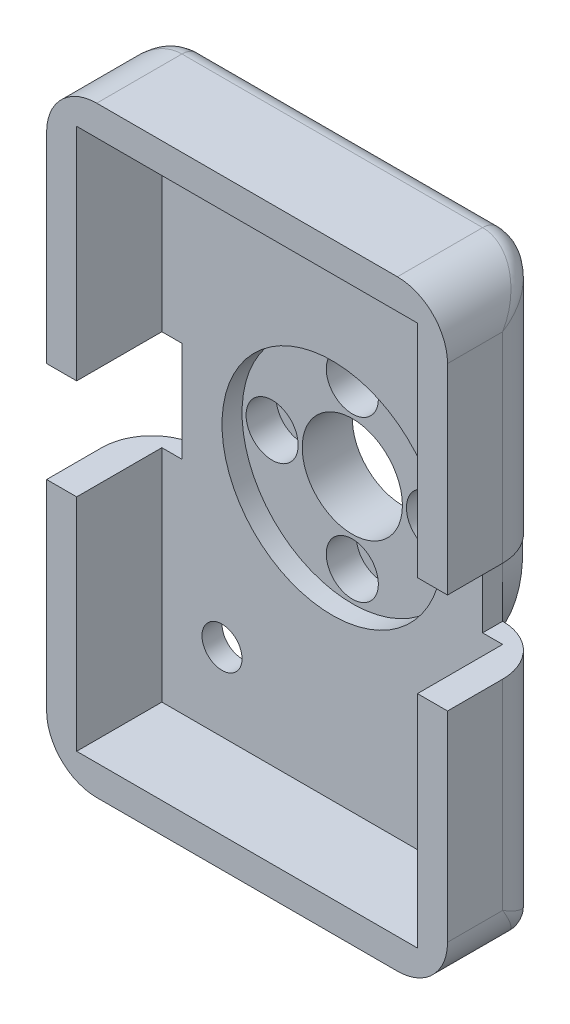
SolidWorks part; units mm, degrees
ref_plane "Front Plane" through (0, 0, 0) normal (0, 0, 1) x (1, 0, 0)
ref_plane "Top Plane" through (0, 0, 0) normal (0, 1, 0) x (1, 0, 0)
ref_plane "Right Plane" through (0, 0, 0) normal (1, 0, 0) x (0, 0, -1)
sketch "Sketch1" plane through (0, 0, 0) normal (0, 0, 1) x (1, 0, 0)
  line L0 (0, -11.559) -> (0, -10.441) construction
  circle A0 centre (0, -3) radius 1.25
  circle A1 centre (-8, -11) radius 1.25
  circle A2 centre (0, -19) radius 1.25
  circle A3 centre (8, -11) radius 1.25
  circle A4 centre (0, -11) radius 11
  spline S0 degree 3 poles (0.1424, -11.5375) (0.0489, -11.5664) (-0.0489, -11.5664) (-0.1424, -11.5375) knots 5.98544 5.98544 5.98544 5.98544 6.580931 6.580931 6.580931 6.580931 weights 1 0.970667 0.970667 1 construction
  spline S1 degree 3 poles (-0.1424, -10.4625) (-0.0489, -10.4336) (0.0489, -10.4336) (0.1424, -10.4625) knots 5.98544 5.98544 5.98544 5.98544 6.580931 6.580931 6.580931 6.580931 weights 1 0.970667 0.970667 1 construction
  dimension "D1" = 22
extrude "Boss-Extrude1" add sketch "Sketch1" along normal blind 5
sketch "Sketch2" plane through (0, 0, 5) normal (0, 0, 1) x (1, 0, 0)
  line L0 (0, 0) -> (0, -11) construction
  line L2 (-20, 19) -> (20, 19)
  line L3 (-20, 19) -> (-20, -41)
  line L4 (-20, -41) -> (20, -41)
  line L5 (20, 19) -> (20, -41)
  line L6 (-20, 19) -> (20, -41) construction
  line L7 (-20, -41) -> (20, 19) construction
  circle A0 centre (0, -11) radius 11 construction
  circle A2 centre (0, -3) radius 1.25 construction
  circle A3 centre (0, -3) radius 1.25
  circle A4 centre (-8, -11) radius 1.25 construction
  circle A5 centre (-8, -11) radius 1.25
  circle A6 centre (0, -19) radius 1.25 construction
  circle A7 centre (0, -19) radius 1.25
  circle A8 centre (8, -11) radius 1.25 construction
  circle A9 centre (8, -11) radius 1.25
  dimension "D1" = 40
  dimension "D2" = 60
extrude "Boss-Extrude3" add sketch "Sketch2" along normal blind 2
fillet "Fillet1" radius 2 2 edges at (0, -41, 5) (0, 19, 5)
sketch "Sketch3" plane through (0, 0, 7) normal (0, 0, 1) x (1, 0, 0)
  circle A0 centre (0, -11) radius 11 construction
  circle A1 centre (0, -11) radius 11
extrude "Cut-Extrude1" cut sketch "Sketch3" against normal blind 2
sketch "Sketch4" plane through (0, 0, 5) normal (0, 0, -1) x (-1, 0, 0)
  line L0 (20, -11) -> (0, -11) construction
  line L1 (20, 19) -> (20, -41) construction
  line L2 (0, -11) -> (0, 9.741) construction
  line L3 (0, 9.741) -> (-11, 9.741) construction
  arc A5 (-13.4, 9.741) -> (-8.6, 9.741) centre (-11, 9.741) ccw construction
  circle A16 centre (-11, 9.741) radius 2
  circle A17 centre (11, 9.741) radius 2
  dimension "D1" = 11
  dimension "D2" = 4
extrude "Cut-Extrude2" cut sketch "Sketch4" against normal blind 2
sketch "Sketch6" plane through (0, 0, 7) normal (0, 0, 1) x (1, 0, 0)
  line L0 (-11, 9.741) -> (-11, -30.259) construction
  line L1 (0, 0) -> (0, 19) construction
  line L2 (20, 19) -> (-20, 19) construction
  circle A0 centre (-11, -30.259) radius 2
  circle A1 centre (11, -30.259) radius 2
  dimension "D1" = 4
extrude "Cut-Extrude3" cut sketch "Sketch6" against normal blind 10
sketch "Sketch7" plane through (0, 0, 7) normal (0, 0, 1) x (1, 0, 0)
  line L0 (20, 19) -> (-20, 19) construction
  line L1 (20, 19) -> (-20, 19)
  line L2 (-20, 19) -> (-20, -41) construction
  line L3 (-20, 19) -> (-20, -41)
  line L4 (-20, -41) -> (20, -41) construction
  line L5 (-20, -41) -> (20, -41)
  line L6 (20, -41) -> (20, 19) construction
  line L7 (20, -41) -> (20, 19)
  line L8 (17, 16) -> (-17, 16)
  line L9 (-17, 16) -> (-17, -38)
  line L10 (-17, -38) -> (17, -38)
  line L11 (17, -38) -> (17, 16)
  dimension "D1" = 3
extrude "Boss-Extrude5" add sketch "Sketch7" along normal up to surface (8.5 mm away)
fillet "Fillet2" radius 5 10 edges at (-20, -41, 11.25) (-20, -40.4142, 5.5858) (-20, -11, 5) (-20, 18.4142, 5.5858) (20, -41, 11.25) (20, -40.4142, 5.5858) (20, -11, 5) (20, 18.4142, 5.5858) (-20, 19, 11.25) (20, 19, 11.25)
sketch "Sketch8" plane through (0, 0, 5) normal (0, 0, 1) x (1, 0, 0)
  circle A0 centre (0, -11) radius 5
  dimension "D1" = 10
extrude "Cut-Extrude4" cut sketch "Sketch8" against normal blind 10
sketch "Sketch10" plane through (0, 0, 5) normal (0, 0, 1) x (1, 0, 0)
  circle A0 centre (-8, -11) radius 2.6
  circle A1 centre (0, -3) radius 2.6
  circle A2 centre (8, -11) radius 2.6
  circle A3 centre (0, -19) radius 2.6
  dimension "D1" = 5.2
extrude "Cut-Extrude5" cut sketch "Sketch10" against normal blind 3
sketch "Sketch11" plane through (0, 0, 5) normal (0, 0, -1) x (-1, 0, 0)
  circle A0 centre (0, -11) radius 15
  circle A1 centre (0, -11) radius 11 construction
  circle A2 centre (0, -11) radius 11
extrude "Boss-Extrude6" add sketch "Sketch11" along normal blind 2
sketch "Sketch12" plane through (0, 0, 5) normal (0, 0, -1) x (-1, 0, 0)
  line L3 (-20, -6) -> (-15, -6)
  line L5 (-15, 17) -> (-15, -11) construction
  line L6 (-20, -6) -> (-20, -16.0163)
  line L7 (-20, -36) -> (-20, 14) construction
  line L8 (-20, -16.0163) -> (-15, -16.0163)
  line L9 (-15, -11) -> (-15, -39) construction
  line L10 (-15, -16.0163) -> (-15, -6)
  line L11 (0, -11.5756) -> (0, 19) construction
  line L12 (-15, 19) -> (15, 19) construction
  line L13 (20, -16.0163) -> (15, -16.0163)
  line L14 (20, -6) -> (20, -16.0163)
  line L15 (20, -6) -> (15, -6)
  line L16 (15, -16.0163) -> (15, -6)
extrude "Cut-Extrude6" cut sketch "Sketch12" against normal up to surface (10.5 mm away) up to face at (0, -11, 15.5)
